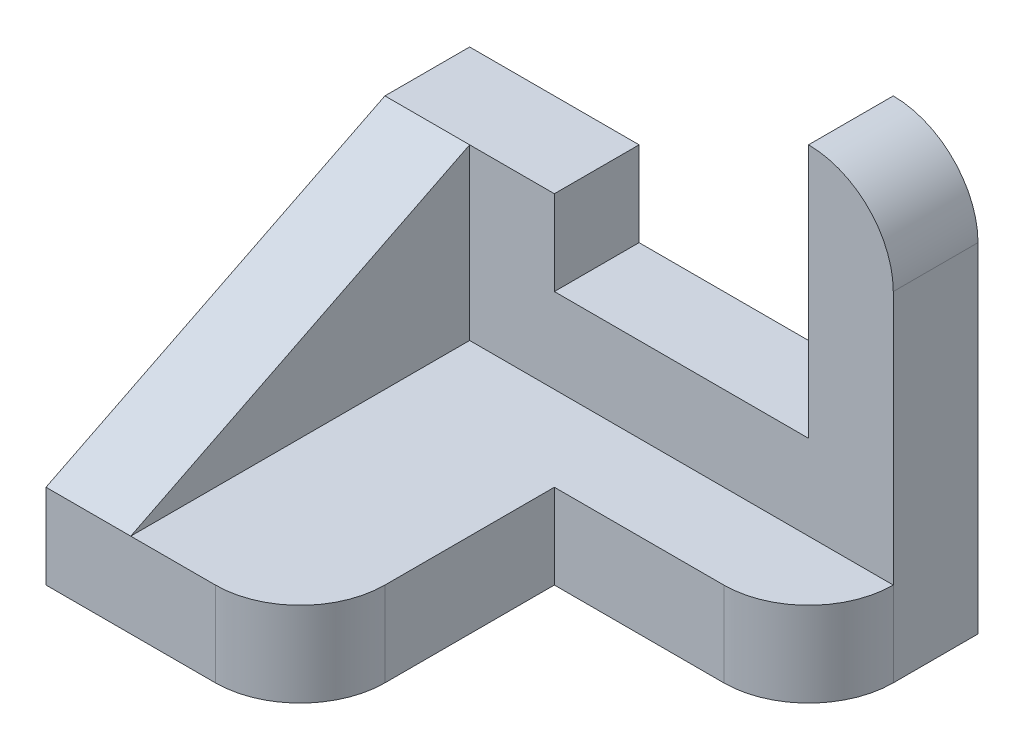
SolidWorks part; units mm, degrees
ref_plane "前基準面" through (0, 0, 0) normal (0, 0, 1) x (1, 0, 0)
ref_plane "上基準面" through (0, 0, 0) normal (0, 1, 0) x (1, 0, 0)
ref_plane "右基準面" through (0, 0, 0) normal (1, 0, 0) x (0, 0, -1)
sketch "草圖1" plane through (0, 0, 0) normal (0, 1, 0) x (1, 0, 0)
  line L0 (0, 0) -> (0, 35.4034) construction
  line L1 (0, 0) -> (0, 5)
  line L2 (0, 5) -> (6, 5)
  line L3 (6, 5) -> (6, 4)
  line L4 (5, 3) -> (3, 3)
  line L5 (3, 3) -> (3, 1)
  line L6 (2, 0) -> (0, 0)
  line L7 (0, 4) -> (6, 4)
  line L8 (2, 5) -> (2, 4)
  line L9 (5, 4) -> (5, 5)
  arc A0 (6, 4) -> (5, 3) centre (5, 4) cw
  arc A1 (3, 1) -> (2, 0) centre (2, 1) cw
  point P10 (6, 3)
  dimension "D5" = 1
  dimension "D1" = 5
  dimension "D2" = 6
  dimension "D3" = 2
  dimension "D4" = 3
  dimension "D6" = 1
  dimension "D7" = 2
  dimension "D8" = 1
extrude "填料-伸長1" add sketch "草圖1" along normal blind 1 contours L8 L2 L1 L7 | A1 L5 L4 A0 L7 L1 L6 | L7 L9 L2 L8 | L9 L7 L3 L2 region at (2.0359, 0, -2.317) region at (1, 0, -4.5) region at (3.5, 0, -4.5) region at (5.5, 0, -4.5)
extrude "填料-伸長2" add sketch "草圖1<3>" along normal blind 2 contours L7 L9 L2 L8 region at (3.5, 0, -4.5)
sketch "草圖1<3>" plane through (0, 0, 0) normal (0, 1, 0) x (1, 0, 0) same geometry as "草圖1"
extrude "填料-伸長3" add sketch "草圖1<4>" along normal blind 3 contours L8 L2 L1 L7 region at (1, 0, -4.5)
sketch "草圖1<4>" plane through (0, 0, 0) normal (0, 1, 0) x (1, 0, 0) same geometry as "草圖1"
extrude "填料-伸長4" add sketch "草圖1<5>" along normal blind 5 contours L9 L7 L3 L2 region at (5.5, 0, -4.5)
sketch "草圖1<5>" plane through (0, 0, 0) normal (0, 1, 0) x (1, 0, 0) same geometry as "草圖1"
fillet "圓角1" radius 1 1 edges at (6, 5, -4.5)
sketch "草圖2" plane through (0, 0, 0) normal (1, 0, 0) x (0, 0, -1)
  line L0 (0, 1) -> (4, 3)
  line L1 (4, 4) -> (4, 1) construction
  line L2 (4, 3) -> (4, 1)
  line L3 (4, 1) -> (0, 1)
  line L4 (3, 0) -> (4, 0) construction
  dimension "D1" = 3
extrude "填料-伸長5" add sketch "草圖2" along normal blind 1
